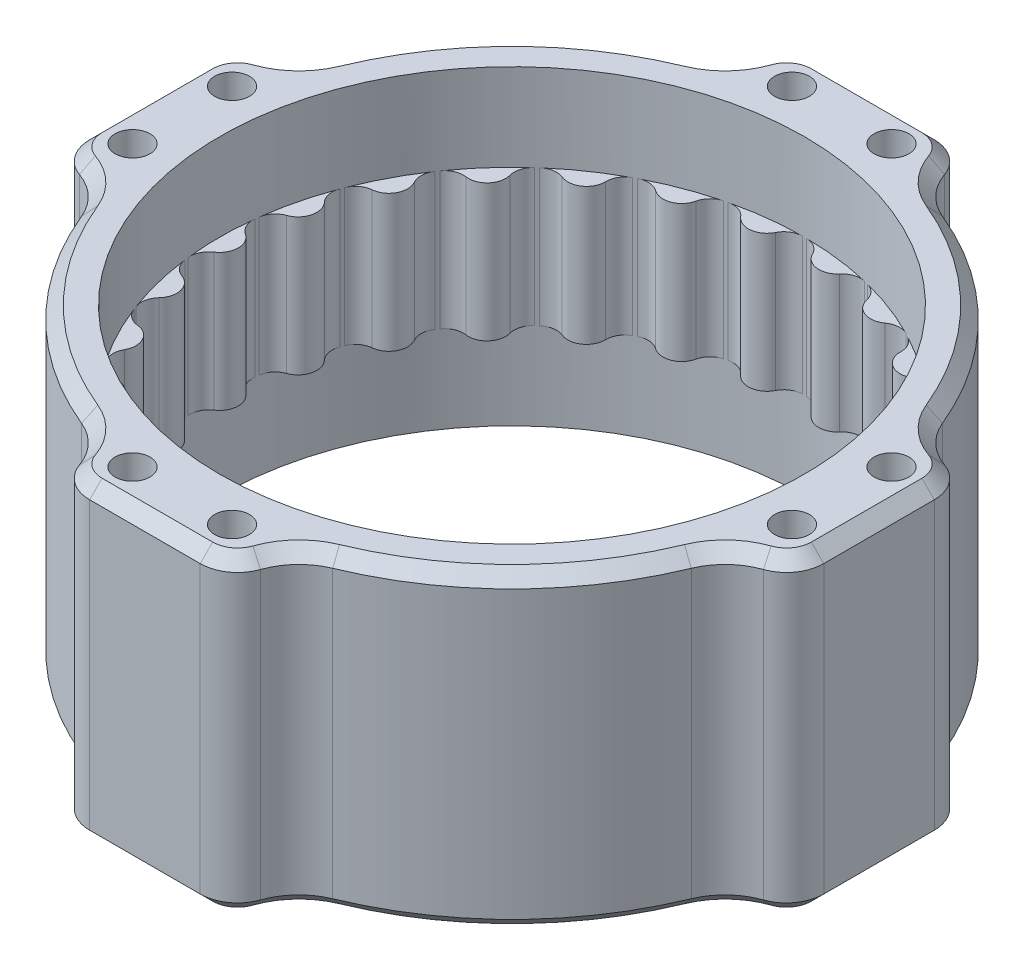
SolidWorks part; units mm, degrees
material "Like ABS"
ref_plane "Front Plane" through (0, 0, 0) normal (0, 0, 1) x (1, 0, 0)
ref_plane "Top Plane" through (0, 0, 0) normal (0, 1, 0) x (1, 0, 0)
ref_plane "Right Plane" through (0, 0, 0) normal (1, 0, 0) x (0, 0, -1)
sketch "Sketch1" plane through (0, 0, 0) normal (0, 1, 0) x (1, 0, 0)
  circle A0 centre (0, 0) radius 23.5
  circle A1 centre (0, 0) radius 26.5
  dimension "D1" = 47
  dimension "D2" = 53
extrude "Boss-Extrude4" add sketch "Sketch1" along normal blind 11
sketch "Sketch15" plane through (0, 11, 0) normal (0, 1, 0) x (1, 0, 0)
  circle A0 centre (0, 0) radius 23.5 construction
  circle A1 centre (-23.5, 0) radius 1.5
  dimension "D1" = 47
  dimension "D2" = 3
extrude "Boss-Extrude5" add sketch "Sketch15" against normal up to surface (11 mm away) up to face at (0, 0, 26.5)
sketch "Sketch7" plane through (0, 0, 0) normal (0, -1, 0) x (1, 0, 0)
  circle A0 centre (0, 0) radius 26.5
  circle A1 centre (0, 0) radius 23.5
  dimension "D1" = 53
  dimension "D2" = 47
extrude "Boss-Extrude6" add sketch "Sketch7" along normal blind 7
fillet "Fillet1" radius 1.5 2 edges at (-23.4521, 5.5, -1.4992) (-23.4521, 5.5, 1.4992)
pattern_circular "CirPattern1" count 26 over 360 about axis through (0, 0, 0) along (0, 1, 0) of "Boss-Extrude5", "Fillet1"
sketch "Sketch16" plane through (0, 11, 0) normal (0, 1, 0) x (1, 0, 0)
  circle A0 centre (0, 0) radius 26.5
  circle A1 centre (0, 0) radius 23.5
  dimension "D1" = 53
  dimension "D2" = 47
extrude "Boss-Extrude7" add sketch "Sketch16" along normal blind 7
sketch "Sketch17" plane through (0, 18, 0) normal (0, 1, 0) x (1, 0, 0)
  line L0 (0, 0) -> (-23.5, 0) construction
  line L1 (-23.5, 0) -> (-29.5, 0) construction
  line L2 (-29.5, 0) -> (-29.5, 7) construction
  line L4 (-29.5, 7) -> (-23.5, 7)
  line L5 (-29.5, 7) -> (-29.5, -7)
  line L6 (-29.5, -7) -> (-23.5, -7)
  line L7 (-23.5, 7) -> (-23.5, -7)
  dimension "D1" = 23.5
  dimension "D2" = 6
  dimension "D3" = 7
  dimension "D4" = 14
extrude "Boss-Extrude8" add sketch "Sketch17" against normal up to surface (25 mm away) up to face at (0, -7, -26.5)
sketch "Sketch18" plane through (0, 18, 0) normal (0, 1, 0) x (1, 0, 0)
  line L0 (-29.5, 7) -> (-26.5, 7) construction
  line L1 (-26.5, 7) -> (-26.5, 4) construction
  line L2 (-26.5, 4) -> (-26.5, -4) construction
  line L3 (-26.5, -4) -> (-26.5, -7) construction
  line L4 (-29.5, -7) -> (-25.5588, -7) construction
  circle A0 centre (-26.5, 4) radius 1.4
  circle A1 centre (-26.5, -4) radius 1.4
  dimension "D2" = 2.8
  dimension "D1" = 3
extrude "Cut-Extrude1" cut sketch "Sketch18" against normal up to surface (25 mm away)
fillet "Fillet2" radius 5 2 edges at (-25.5588, 5.5, 7) (-25.5588, 5.5, -7)
fillet "Fillet3" radius 3 2 edges at (-29.5, 5.5, 7) (-29.5, 5.5, -7)
pattern_circular "CirPattern2" count 4 over 360 about axis through (0, 0, 0) along (0, 1, 0) of "Fillet3", "Boss-Extrude8", "Fillet2", "Cut-Extrude1"
chamfer "Chamfer1" distance 1 angle 45 48 edges at (-18.7383, -7, -18.7383) (-18.7383, 18, 18.7383) (-25.6906, -7, 8.3659) (-25.6906, 18, -8.3659) (-29.5, -7, 0) (-29.5, 18, 0) (-25.6906, 18, 8.3659) (-28.9447, 18, -6.1817) (-28.9447, 18, 6.1817) (-25.6906, -7, -8.3659) (-28.9447, -7, -6.1817) (-28.9447, -7, 6.1817) (18.7383, 18, 18.7383) (-18.7383, -7, 18.7383) (8.3659, -7, 25.6906) (-8.3659, 18, 25.6906) (18.7383, 18, -18.7383) (18.7383, -7, 18.7383) (25.6906, -7, -8.3659) (25.6906, 18, 8.3659) (-18.7383, 18, -18.7383) (18.7383, -7, -18.7383) (-8.3659, -7, -25.6906) (8.3659, 18, -25.6906) (0, -7, 29.5) (0, 18, 29.5) (8.3659, 18, 25.6906) (-6.1817, 18, 28.9447) (6.1817, 18, 28.9447) (-8.3659, -7, 25.6906) (-6.1817, -7, 28.9447) (6.1817, -7, 28.9447) (29.5, -7, 0) (29.5, 18, 0) (25.6906, 18, -8.3659) (28.9447, 18, 6.1817) (28.9447, 18, -6.1817) (25.6906, -7, 8.3659) (28.9447, -7, 6.1817) (28.9447, -7, -6.1817) (0, -7, -29.5) (0, 18, -29.5) (-8.3659, 18, -25.6906) (6.1817, 18, -28.9447) (-6.1817, 18, -28.9447) (8.3659, -7, -25.6906) (6.1817, -7, -28.9447) (-6.1817, -7, -28.9447)
